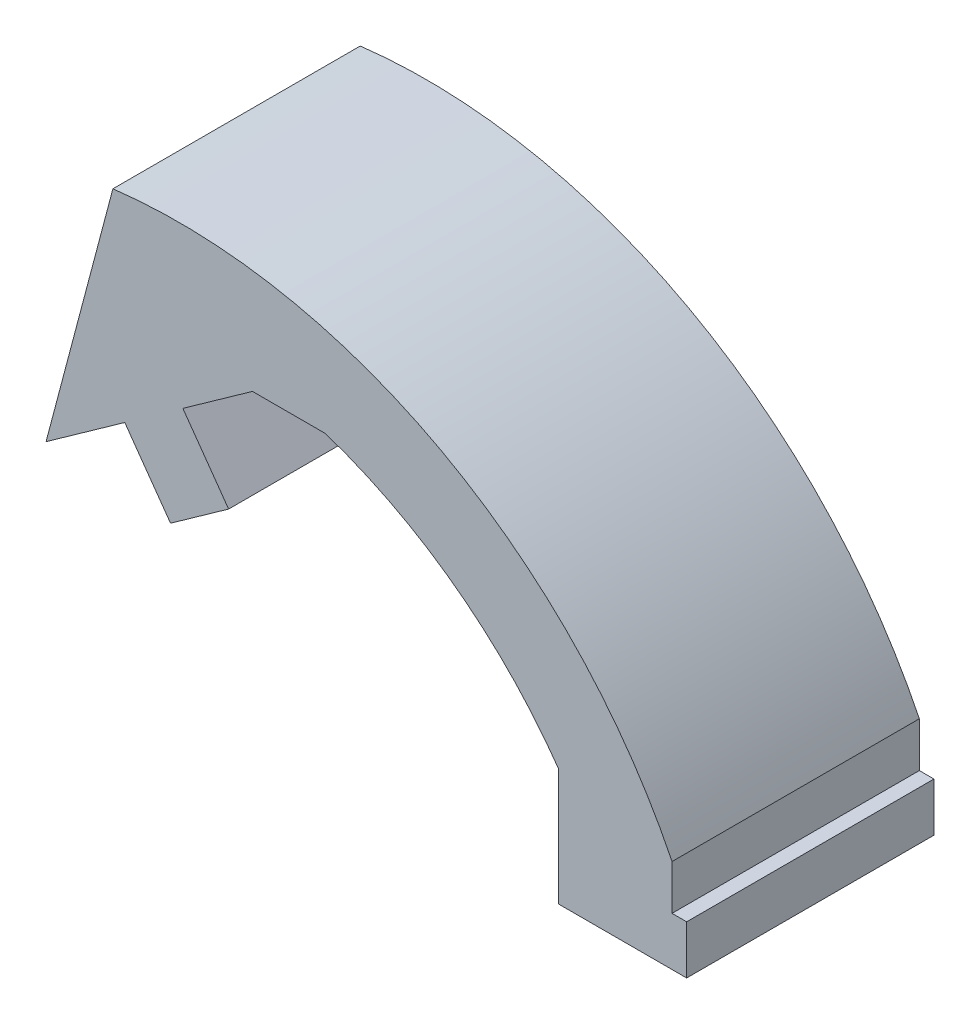
SolidWorks part; units mm, degrees
ref_plane "Front Plane" through (0, 0, 0) normal (0, 0, 1) x (1, 0, 0)
ref_plane "Top Plane" through (0, 0, 0) normal (0, 1, 0) x (1, 0, 0)
ref_plane "Right Plane" through (0, 0, 0) normal (1, 0, 0) x (0, 0, -1)
sketch "Sketch4" plane through (0, 0, 0) normal (0, 0, 1) x (1, 0, 0)
  line L17 (-17.2722, 0.35) -> (-17.2722, 6.35)
  line L36 (-33.0008, 15.2891) -> (-29.2508, 15.2891)
  line L37 (-36.5743, 12.7484) -> (-34.2247, 9.4436)
  line L39 (-43.6007, 7.7527) -> (-40.1675, 20.7167)
  line L51 (-17.2722, 0.35) -> (-11.4125, 0.35)
  line L52 (-11.4542, 5.1546) -> (-11.4542, 2.85)
  line L57 (-34.2247, 9.4436) -> (-37.2077, 7.3227)
  line L58 (-11.4125, 0.35) -> (-10.7042, 0.35)
  line L60 (-11.4542, 2.85) -> (-10.7042, 2.85)
  line L61 (-10.7042, 0.35) -> (-10.7042, 2.85)
  line L62 (-37.2077, 7.3227) -> (-39.5574, 10.6274)
  line L64 (-39.5574, 10.6274) -> (-43.6007, 7.7527)
  line L85 (-29.2508, 13.2891) -> (-29.2508, 15.2891)
  line L87 (-33.0008, 15.2891) -> (-36.5743, 12.7484)
  arc A6 (-11.4542, 5.1546) -> (-40.1675, 20.7167) centre (-36.7643, -7.2744) ccw
  arc A8 (-17.2722, 6.35) -> (-29.2508, 15.2891) centre (-36.7643, -7.2744) ccw
  dimension "D2" = 11.4125
  dimension "D3" = 28.1972
  dimension "D6" = 23.7816
  dimension "D4" = 0.75
  dimension "D5" = 2.5
  dimension "D7" = 10.7042
  dimension "D8" = 17.2722
  dimension "D9" = 29.2508
  dimension "D10" = 33.0008
  dimension "D11" = 34.2247
  dimension "D12" = 36.5743
  dimension "D13" = 36.7643
  dimension "D14" = 37.2077
  dimension "D15" = 0.35
  dimension "D16" = 40.1675
  dimension "D17" = 43.6007
  dimension "D18" = 5.1546
  dimension "D19" = 7.3227
  dimension "D20" = 13.2891
extrude "Boss-Extrude1" add sketch "Sketch4" against normal blind 12.7 contours L36 L87 L37 L57 L62 L64 L39 A6 L52 L60 L61 L58 L51 L17 A8
